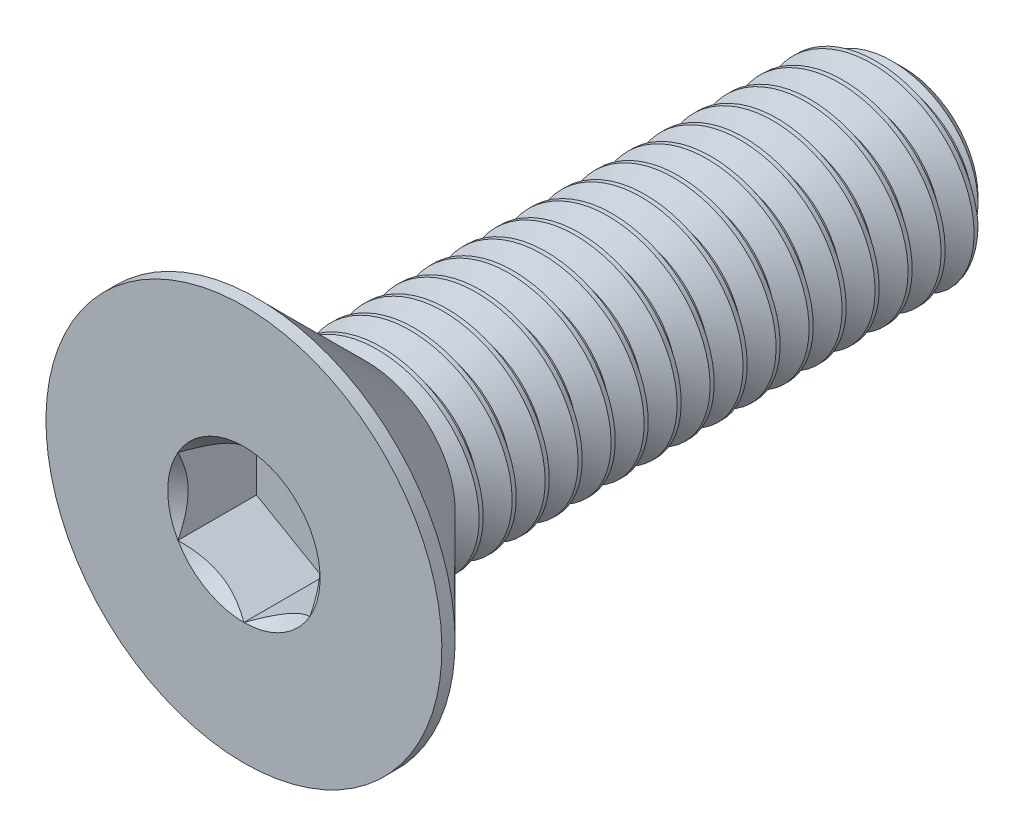
SolidWorks part; units mm, degrees
ref_plane "Front" through (0, 0, 0) normal (0, 0, 1) x (1, 0, 0)
ref_plane "Top" through (0, 0, 0) normal (0, 1, 0) x (1, 0, 0)
ref_plane "Right" through (0, 0, 0) normal (1, 0, 0) x (0, 0, -1)
sketch "Sketch1" plane through (0, 0, 0) normal (1, 0, 0) x (0, 0, -1)
  line L0 (0, 3) -> (0.2, 3) construction
  line L1 (0.2, 3) -> (1.7, 1.5) construction
  line L2 (0, 1.5) -> (10, 1.5)
  line L3 (10, 1.5) -> (10, 0)
  line L4 (10, 0) -> (0, 0)
  line L5 (0, 0) -> (0, 3) construction
  line L6 (0, 3) -> (0, -3) construction
  line L7 (10, 1.5) -> (10, -1.5) construction
  line L8 (0, -3) -> (0.2, -3) construction
  line L9 (0.2, -3) -> (1.7, -1.5) construction
  line L11 (0, 1.5) -> (0, 0)
  line L12 (1.7, 1.5) -> (1.7, 0) construction
  dimension "Head Ht" = 1.7
  dimension "Head Dia" = 6
  dimension "Dia" = 3
  dimension "Lg" = 10
  dimension "Head Angle" = 90
revolve "Revolve1" add sketch "Sketch1" angle 360 mid plane about L4
sketch "Sketch3" plane through (0, 0, -10) normal (0, 0, -1) x (-1, 0, 0)
  circle A0 centre (0, 0) radius 1.5
curve "Helix/Spiral1" pitch 0.5 height 10 radius 1.5 centre (0, 0, -10) axis (0, 0, 1) start towards (0, 1, 0)
sketch "Sketch2" plane through (0, 0, 0) normal (1, 0, 0) x (0, 0, -1)
  line L0 (10, 1.5) -> (10.4375, 1.5)
  line L1 (10.4375, 1.5) -> (10.25, 1.1752)
  line L2 (10.25, 1.1752) -> (10.1875, 1.1752)
  line L3 (10.1875, 1.1752) -> (10, 1.5)
  line L4 (10.0938, 1.3376) -> (10.3437, 1.3376) construction
  dimension "D1" = 60
  dimension "D2" = 0.0625
  dimension "D3" = 0.25
chamfer "Chamfer1" distance 0.375 angle 45 1 edges at (0, 1.5, -10)
sweep "Cut-Sweep1" cut profiles "Sketch2" path "Helix/Spiral1" align with end faces yes
sketch "Sketch7" plane through (0, 0, 0) normal (1, 0, 0) x (0, 0, -1)
  line L0 (0, 3) -> (0.2, 3) construction
  line L1 (0.2, 3) -> (1.7, 1.5) construction
  line L2 (0, 3) -> (0.2, 3)
  line L3 (0.2, 3) -> (1.7, 1.5)
  line L4 (1.7, 1.5) -> (1.7, 0) construction
  line L5 (1.7, 1.5) -> (1.7, 0)
  line L7 (0, 0) -> (0, 3) construction
  line L8 (0, 0) -> (0, 3)
  line L9 (0, 0) -> (1.7, 0)
  line L10 (3.3, 0) -> (-3.3, 0) construction
revolve "Revolve2" add sketch "Sketch7" angle 360 mid plane about L9
ref_plane "Plane1" through (0, 0, -1.7) normal (0, 0, 1) x (1, 0, 0)
sketch "Sketch8" plane through (0, 0, -1.7) normal (0, 0, 1) x (1, 0, 0)
  circle A0 centre (0, 0) radius 1.5
extrude "Boss-Extrude1" add sketch "Sketch8" against normal through all draft 45
sketch "Sketch5" plane through (0, 0, 0) normal (0, 0, 1) x (1, 0, 0)
  line L1 (1, -0.5774) -> (1, 0.5774)
  line L2 (1, 0.5774) -> (0, 1.1547)
  line L3 (0, 1.1547) -> (-1, 0.5774)
  line L4 (-1, 0.5774) -> (-1, -0.5774)
  line L5 (-1, -0.5774) -> (0, -1.1547)
  line L6 (0, -1.1547) -> (1, -0.5774)
  circle A0 centre (0, 0) radius 1 construction
  dimension "Hex" = 2
extrude "Cut-Extrude2" cut sketch "Sketch5" against normal blind 1.19
sketch "Sketch6" plane through (0, 0, 0) normal (0, 0, 1) x (1, 0, 0)
  circle A0 centre (0, 0) radius 1.1547
extrude "Cut-Extrude3" cut sketch "Sketch6" against normal blind 1.19 draft 45
sketch "Sketch9" [suppressed] plane through (0, 0, -5.5) normal (0, 0, 1) x (1, 0, 0)
  circle A1 centre (0, 0) radius 5
  circle A2 centre (0, 0) radius 5
  point P0 (0, 5)
  dimension "D1" = 0
extrude "Boss-Extrude2" [suppressed] add sketch "Sketch9" against normal offset from surface (18.5 mm away) 26 up to face at (0, 1.125, -10)
fillet "Fillet1" [suppressed] radius 0.3
sketch "Sketch10" plane through (0, 0, 0) normal (1, 0, 0) x (0, 0, -1)
  line L0 (10, 1.5) -> (10, -1.5) construction
  point P0 (9.25, -1.5)
  dimension "D1" = 0.75
equation "\"D3@Helix/Spiral1\" = \"Lg@Sketch1\""
equation "\"D2@Sketch2\" = \"D4@Helix/Spiral1\" * .125"
equation "\"D3@Sketch2\" = \"D4@Helix/Spiral1\" * .5"
equation "\"D1@Chamfer1\" = \"D4@Helix/Spiral1\" * .75"
equation "\"D1@Cut-Extrude2\" = \"Head Ht@Sketch1\" * .7"
equation "\"D1@Sketch10\" = \"D4@Helix/Spiral1\" * 1.5"
equation "\"D1@Cut-Extrude3\" = \"D1@Cut-Extrude2\""
equation "\"D1@Fillet1\" = \"Dia@Sketch1\" * .1"
